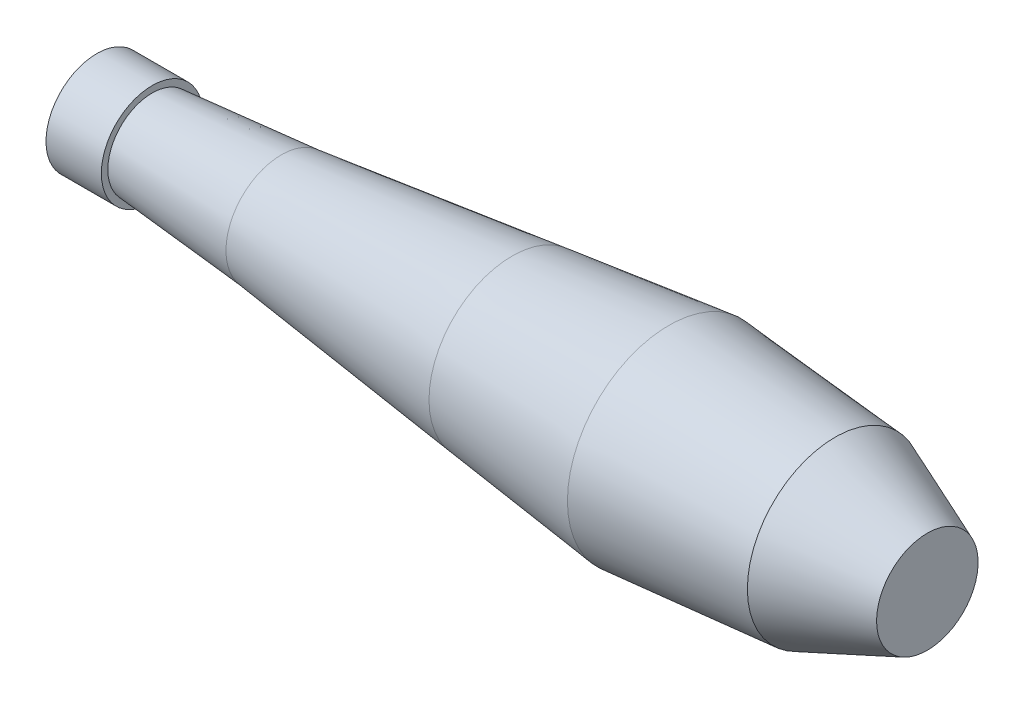
SolidWorks part; units mm, degrees
material "Oak"
ref_plane "Front Plane" through (0, 0, 0) normal (0, 0, 1) x (1, 0, 0)
ref_plane "Top Plane" through (0, 0, 0) normal (0, 1, 0) x (1, 0, 0)
ref_plane "Right Plane" through (0, 0, 0) normal (1, 0, 0) x (0, 0, -1)
sketch "Sketch1" plane through (0, 0, 0) normal (0, 0, 1) x (1, 0, 0)
  line L0 (0, 0) -> (90, 0) construction
  line L1 (0, 0) -> (0, 5.5)
  line L2 (0, 5.5) -> (6, 5.5)
  line L3 (6, 5.5) -> (6, 4.8)
  line L4 (6, 4.8) -> (20, 6)
  line L5 (20, 6) -> (45, 9)
  line L6 (45, 9) -> (62, 11)
  line L7 (62, 11) -> (80, 9.5)
  line L8 (80, 9.5) -> (90, 5.5)
  line L9 (90, 5.5) -> (90, 0)
  line L10 (90, 0) -> (0, 0)
  dimension "D1" = 90
  dimension "D2" = 5.5
  dimension "D3" = 6
  dimension "D4" = 0.7
  dimension "D5" = 5.5
  dimension "D6" = 14
  dimension "D7" = 1.2
  dimension "D8" = 25
  dimension "D9" = 3
  dimension "D10" = 17
  dimension "D11" = 2
  dimension "D12" = 18
  dimension "D13" = 1.5
revolve "Revolve1" add sketch "Sketch1" angle 360 about L0
